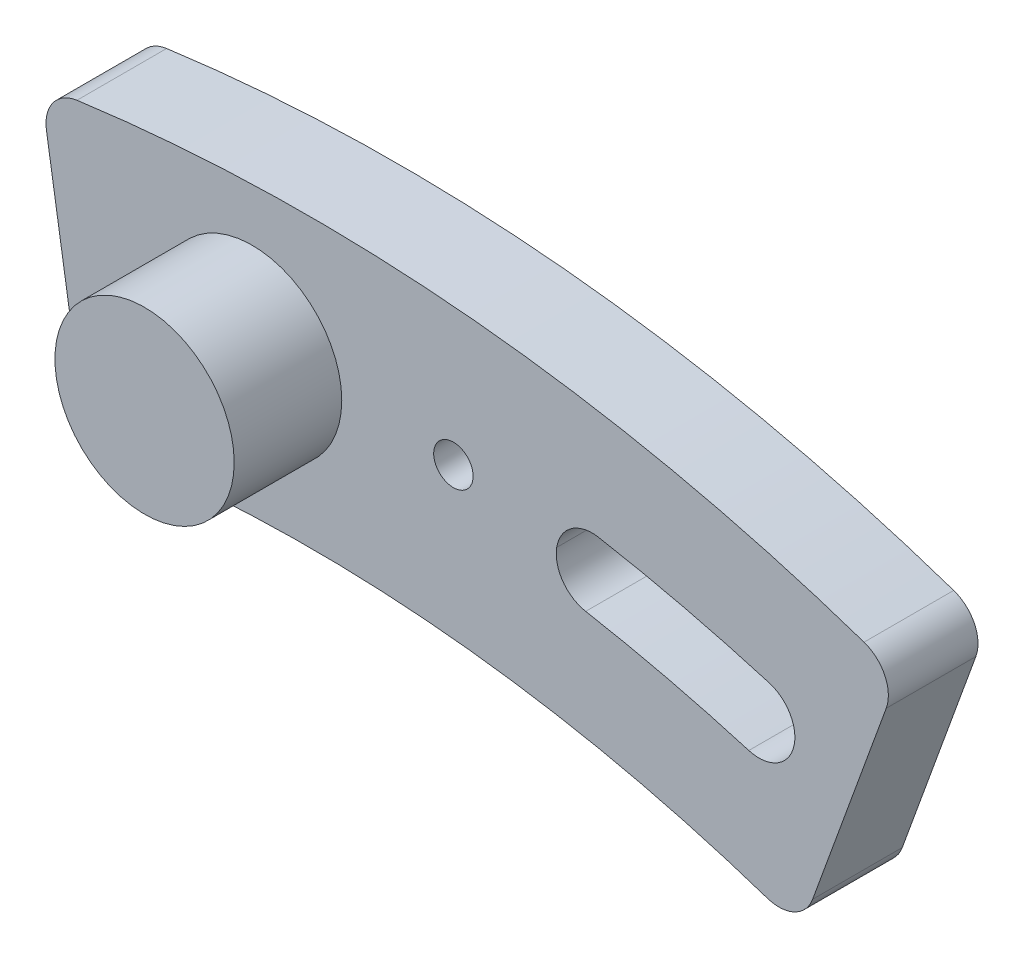
SolidWorks part; units mm, degrees
ref_plane "Front Plane" through (0, 0, 0) normal (0, 0, 1) x (1, 0, 0)
ref_plane "Top Plane" through (0, 0, 0) normal (0, 1, 0) x (1, 0, 0)
ref_plane "Right Plane" through (0, 0, 0) normal (1, 0, 0) x (0, 0, -1)
sketch "Sketch1" plane through (0, 0, 0) normal (0, 0, 1) x (1, 0, 0)
  line L0 (0, 0) -> (0, 80) construction
  line L1 (0, 0) -> (32.8339, 90.2105) construction
  line L2 (0, 0) -> (-6.116, 6.116) construction
  line L5 (27.3616, 75.1754) -> (32.8339, 90.2105)
  line L6 (0, 0) -> (-15.0177, 94.8181) construction
  line L7 (0, 0) -> (15.0177, 94.8181) construction
  line L8 (27.5717, 85.6726) -> (26.3463, 81.865)
  line L9 (0, 0) -> (25.144, 82.2422) construction
  line L10 (-15.0177, 94.8181) -> (-12.5148, 79.0151)
  line L11 (15.0177, 94.8181) -> (12.5148, 79.0151)
  line L14 (-13.9378, 88) -> (8, 88) construction
  line L15 (-0.5, 95.9987) -> (-0.5, 79.9984)
  line L23 (0, 0) -> (-53.662, 92.9453) construction
  line L44 (44.4908, 78.2349) -> (44.4904, 78.2343)
  line L45 (44.4882, 78.2355) -> (44.4908, 78.2349)
  line L58 (22.7288, 87.0833) -> (22.7287, 87.0828)
  arc A2 (27.3616, 75.1754) -> (-12.5148, 79.0151) centre (0, 0) ccw
  arc A3 (29.4137, 80.8136) -> (13.4534, 84.9412) centre (0, 0) ccw
  arc A4 (30.7818, 84.5723) -> (14.0791, 88.892) centre (0, 0) ccw
  arc A5 (32.8339, 90.2105) -> (-15.0177, 94.8181) centre (0, 0) ccw
  circle A8 centre (-3.227, 88) radius 5
  circle A10 centre (8, 88) radius 1.1
  point P28 (-30.0281, 84.7967)
  point P40 (-22.5352, 87.1334)
  point P45 (-14.8562, 88.766)
  point P55 (-44.3168, 78.3334)
  point P68 (44.3168, 78.3334)
  point P79 (14.8562, 88.766)
  point P80 (22.5352, 87.1334)
  point P81 (30.0281, 84.7967)
  point P106 (0, 0)
  point P169 (0, 0)
  dimension "D1" = 192
  dimension "D2" = 180
  dimension "D3" = 172
  dimension "D4" = 160
  dimension "D10" = 2.2
  dimension "D6" = 10
  dimension "D5" = 20
  dimension "D7" = 9
  dimension "D8" = 50
  dimension "D11" = 8
  dimension "D13" = 3
extrude "Boss-Extrude1" add sketch "Sketch1" along normal blind 5 contours A5 L10 A2 L5
extrude "Cut-Extrude2" cut sketch "Sketch1<13>" along normal blind 10 contours L8 A4 L11 A3 | A10 region at (20.4066, 85.5271, 0)
sketch "Sketch1<13>" plane through (0, 0, 0) normal (0, 0, 1) x (1, 0, 0) same geometry as "Sketch1"
fillet "Fillet1" radius 2 8 edges at (26.3463, 81.865, 2.5) (27.5717, 85.6726, 2.5) (14.0791, 88.892, 2.5) (13.4534, 84.9412, 2.5) (-12.5148, 79.0151, 2.5) (-15.0177, 94.8181, 2.5) (27.3616, 75.1754, 2.5) (32.8339, 90.2105, 2.5)
extrude "Boss-Extrude2" add sketch "Sketch1<14>" along normal blind 11 contours L15 A8 | L15 A8 region at (-3.9805, 88, 0) region at (0.4296, 88, 0)
sketch "Sketch1<14>" plane through (0, 0, 0) normal (0, 0, 1) x (1, 0, 0) same geometry as "Sketch1"
